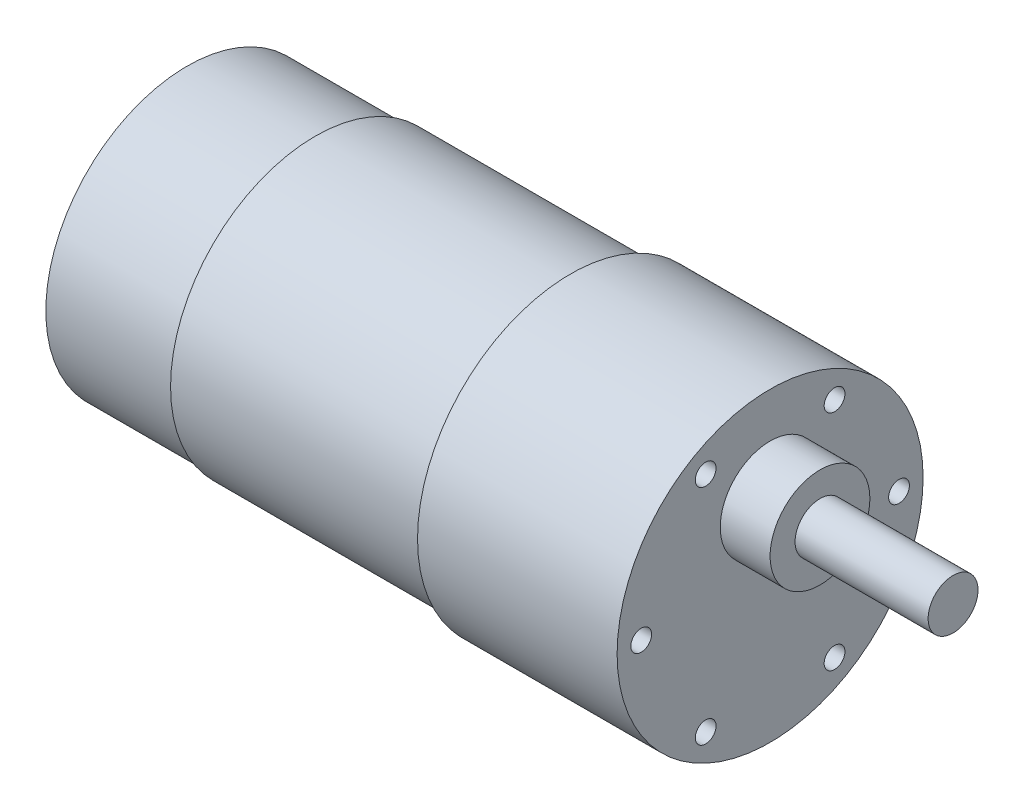
SolidWorks part; units mm, degrees
ref_plane "Front Plane" through (0, 0, 0) normal (0, 0, 1) x (1, 0, 0)
ref_plane "Top Plane" through (0, 0, 0) normal (0, 1, 0) x (1, 0, 0)
ref_plane "Right Plane" through (0, 0, 0) normal (1, 0, 0) x (0, 0, -1)
sketch "SK_Gearbox" plane through (0, 0, 0) normal (1, 0, 0) x (0, 0, -1)
  circle A0 centre (0, 0) radius 18.4
  dimension "D1" = 36.8
extrude "EX_Gearbox" add sketch "SK_Gearbox" against normal blind 24
ref_plane "PL_Ym24" through (-24, 0, 0) normal (1, 0, 0) x (0, 0, -1)
sketch "SK_Motor" plane through (-24, 0, 0) normal (1, 0, 0) x (0, 0, -1)
  circle A0 centre (0, 0) radius 17.4
  dimension "D1" = 34.8
extrude "EX_Motor" add sketch "SK_Motor" against normal blind 30.7
ref_plane "PL_Ym54_7" through (-54.7, 0, 0) normal (1, 0, 0) x (0, 0, -1)
sketch "SK_Encoder" plane through (-54.7, 0, 0) normal (1, 0, 0) x (0, 0, -1)
  circle A0 centre (0, 0) radius 17
  dimension "D1" = 34
extrude "EX_Encoder" add sketch "SK_Encoder" against normal blind 15.4
sketch "SK_Bushing" plane through (0, 0, 0) normal (1, 0, 0) x (0, 0, -1)
  circle A0 centre (0, 7) radius 6
  dimension "D2" = 12
  dimension "D1" = 7
extrude "EX_Bushing" add sketch "SK_Bushing" along normal blind 6
ref_plane "PL_Yp6" through (6, 0, 0) normal (1, 0, 0) x (0, 0, -1)
sketch "SK_Shaft" plane through (6, 0, 0) normal (1, 0, 0) x (0, 0, -1)
  circle A0 centre (0, 7) radius 3
  dimension "D2" = 6
  dimension "D1" = 7
extrude "EX_Shaft" add sketch "SK_Shaft" along normal blind 16
sketch "SK_MountHoles_6xM3" plane through (0, 0, 0) normal (1, 0, 0) x (0, 0, -1)
  circle A0 centre (-15.5, 0) radius 1.25
  circle A1 centre (-7.75, 13.4234) radius 1.25
  circle A2 centre (7.75, 13.4234) radius 1.25
  circle A3 centre (15.5, 0) radius 1.25
  circle A4 centre (7.75, -13.4234) radius 1.25
  circle A5 centre (-7.75, -13.4234) radius 1.25
  dimension "D2" = 2.5
  dimension "D5" = 2.5
  dimension "D8" = 2.5
  dimension "D10" = 2.5
  dimension "D13" = 2.5
  dimension "D16" = 2.5
  dimension "D1" = 15.5
  dimension "D3" = 7.75
  dimension "D4" = 13.4234
  dimension "D6" = 7.75
  dimension "D7" = 13.4234
  dimension "D9" = 15.5
  dimension "D11" = 7.75
  dimension "D12" = 13.4234
  dimension "D14" = 7.75
  dimension "D15" = 13.4234
extrude "CUT_MountHoles_6xM3" cut sketch "SK_MountHoles_6xM3" against normal blind 3
ref_axis "AX_X" through (0, 0, -20.24) along (0, 0, 1)
ref_axis "AX_Y" through (26.605, 0, 0) along (-1, 0, 0)
ref_axis "AX_Z" through (0, 20.24, 0) along (0, -1, 0)
ref_plane "PL_Zp7" through (0, 7, 0) normal (0, 1, 0) x (1, 0, 0)
sketch "SK_F_IF_Shaft" plane through (0, 7, 0) normal (0, 1, 0) x (1, 0, 0)
  point P0 (0, 0)
